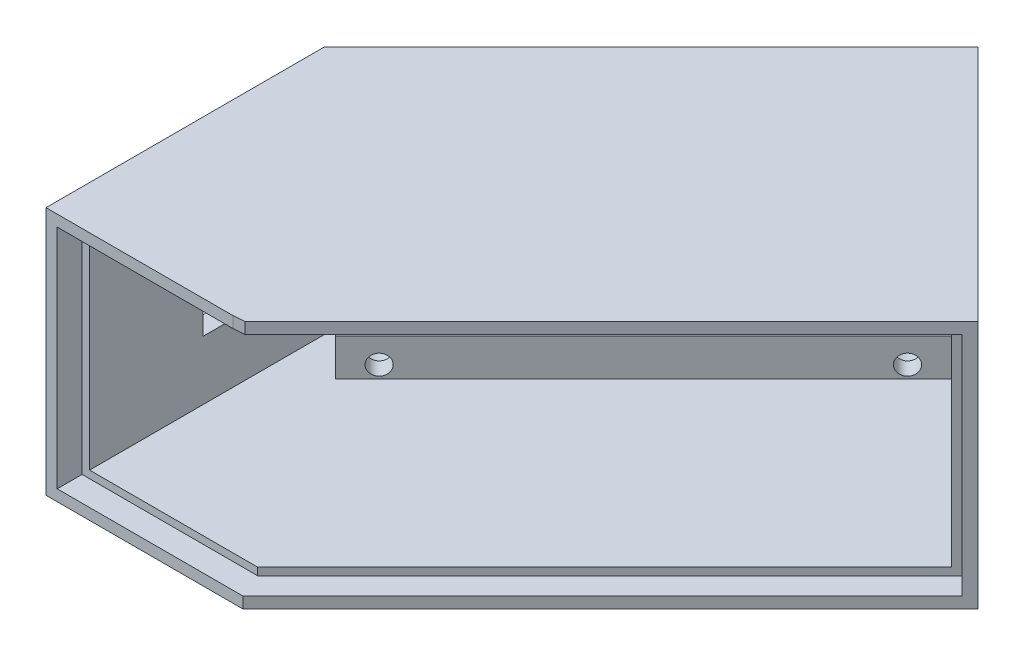
SolidWorks part; units mm, degrees
ref_plane "Спереди" through (0, 0, 0) normal (0, 0, 1) x (1, 0, 0)
ref_plane "Сверху" through (0, 0, 0) normal (0, 1, 0) x (1, 0, 0)
ref_plane "Справа" through (0, 0, 0) normal (1, 0, 0) x (0, 0, -1)
sketch "Sketch1" plane through (0, 0, 0) normal (0, 1, 0) x (1, 0, 0)
  line L0 (-43.3594, -5.3943) -> (-43.3594, 35.3164)
  line L1 (-43.3594, 35.3164) -> (9.115, 87.7907)
  line L2 (9.115, 87.7907) -> (44.4704, 52.4354)
  line L3 (44.4704, 52.4354) -> (-13.3594, -5.3943)
  line L4 (-13.3594, -5.3943) -> (-43.3594, -5.3943)
  dimension "D1" = 74.21
  dimension "D3" = 135
  dimension "D4" = 30
  dimension "D5" = 50
extrude "Boss-Extrude1" add sketch "Sketch1" along normal blind 40
shell "Shell1" thickness 3 removed face at (-28.3594, 20, 5.3943) removed face at (15.5555, 20, -23.5205)
sketch "Sketch6" plane through (-3.9825, 0, -3.9825) normal (0.7071, 0, 0.7071) x (0.7071, 0, -0.7071)
  line L0 (-13.2609, 38.2) -> (66.7227, 38.2)
  line L1 (-13.2609, 40) -> (-13.2609, 37) construction
  line L2 (66.7227, 38.2) -> (66.7227, 1.8)
  line L3 (66.7227, 1.8) -> (-13.2609, 1.8)
  line L4 (-13.2609, 3) -> (-13.2609, 0) construction
  line L5 (-13.2609, 40) -> (68.5227, 40) construction
  line L6 (-13.2609, 0) -> (68.5227, 0) construction
  line L7 (68.5227, 40) -> (68.5227, 0) construction
  line L8 (-13.2609, 38.2) -> (-13.2609, 40)
  line L9 (-13.2609, 40) -> (68.5227, 40)
  line L10 (68.5227, 40) -> (68.5227, 0)
  line L11 (68.5227, 0) -> (-13.2609, 0)
  line L12 (-13.2609, 0) -> (-13.2609, 1.8)
  dimension "D1" = 1.8
  dimension "D2" = 1.8
  dimension "D3" = 1.8
extrude "Boss-Extrude2" add sketch "Sketch6" along normal blind 4
sketch "Sketch7" plane through (0, 0, 5.3943) normal (0, 0, 1) x (1, 0, 0)
  line L0 (-13.3594, 1.8) -> (-41.5594, 1.8)
  line L1 (-41.5594, 1.8) -> (-41.5594, 38.2)
  line L2 (-41.5594, 38.2) -> (-13.3594, 38.2)
  line L3 (-43.3594, 40) -> (-43.3594, 0) construction
  line L4 (-13.3594, 38.2) -> (-13.3594, 40)
  line L5 (-13.3594, 40) -> (-43.3594, 40)
  line L6 (-43.3594, 40) -> (-43.3594, 0)
  line L7 (-43.3594, 0) -> (-13.3594, 0)
  line L8 (-13.3594, 0) -> (-13.3594, 1.8)
  dimension "D1" = 1.8
extrude "Boss-Extrude3" add sketch "Sketch7" along normal blind 4
sketch "Sketch8" plane through (0, 0, 0) normal (0, -1, 0) x (1, 0, 0)
  line L0 (-13.3594, 9.3943) -> (-11.7025, 9.3943)
  line L1 (-11.7025, 9.3943) -> (-10.5309, 8.2228)
  line L2 (-10.5309, 8.2228) -> (-13.3594, 5.3943)
  line L3 (-13.3594, 5.3943) -> (-13.3594, 9.3943)
  line L4 (-10.5309, 8.2228) -> (47.2988, -49.607) construction
extrude "Boss-Extrude4" add sketch "Sketch8" against normal up to surface (1.8 mm away) up to face at (16.3333, 1.8, -21.4699)
sketch "Sketch9" plane through (0, 40, 0) normal (0, 1, 0) x (1, 0, 0)
  line L0 (-13.3594, -5.3943) -> (-10.5309, -8.2228)
  line L1 (-10.5309, -8.2228) -> (-11.5537, -9.2455)
  line L2 (-11.5537, -9.2455) -> (-13.3594, -9.3943)
  line L3 (-13.3594, -9.3943) -> (-13.3594, -5.3943)
  line L4 (47.2988, 49.607) -> (-10.5309, -8.2228) construction
extrude "Boss-Extrude5" add sketch "Sketch9" against normal up to surface (1.8 mm away) up to face at (16.3333, 38.2, -21.4699)
sketch "Sketch10" plane through (-37.2165, 0, -37.2165) normal (0.7071, 0, 0.7071) x (0.7071, 0, -0.7071)
  line L0 (65.5227, 20) -> (-4.4446, 20) construction
  line L1 (65.5227, 37) -> (65.5227, 3) construction
  line L2 (-4.4446, 37) -> (-4.4446, 3) construction
  line L3 (60.5227, 35) -> (60.5227, 5) construction
  line L4 (68.5227, 40) -> (68.5227, 0) construction
  line L5 (0.5227, 35) -> (0.5227, 5) construction
  line L6 (60.5227, 35) -> (0.5227, 35) construction
  circle A0 centre (60.5227, 35) radius 1.6
  circle A1 centre (60.5227, 5) radius 1.6
  circle A2 centre (0.5227, 35) radius 1.6
  circle A3 centre (0.5227, 5) radius 1.6
  point P8 (60.5227, 20)
  point P11 (68.5227, 20)
  dimension "D3" = 3.2
  dimension "D1" = 30
  dimension "D2" = 8
  dimension "D4" = 60
extrude "Cut-Extrude6" cut sketch "Sketch10" against normal through all
sketch "Sketch11" plane through (-40.3594, 0, 0) normal (1, 0, 0) x (0, 0, -1)
  line L0 (19.2076, 37) -> (19.2076, 3) construction
  line L1 (34.0737, 37) -> (-5.3943, 37) construction
  line L2 (34.0737, 3) -> (-5.3943, 3) construction
  line L4 (12.8076, 12.5) -> (25.6076, 12.5)
  line L5 (12.8076, 12.5) -> (12.8076, 27.5)
  line L6 (12.8076, 27.5) -> (25.6076, 27.5)
  line L7 (25.6076, 12.5) -> (25.6076, 27.5)
  line L8 (12.8076, 12.5) -> (25.6076, 27.5) construction
  line L9 (12.8076, 27.5) -> (25.6076, 12.5) construction
  point P6 (19.2076, 20)
  dimension "D1" = 15
  dimension "D2" = 12.8
extrude "Cut-Extrude7" cut sketch "Sketch11" against normal up to surface (3 mm away) up to face at (-43.3594, 20, -12.961)
sketch "Sketch12" plane through (-37.2165, 0, -37.2165) normal (0.7071, 0, 0.7071) x (0.7071, 0, -0.7071)
  line L0 (65.5227, 37) -> (-4.4446, 3) construction
  line L1 (-4.4446, 37) -> (-4.4446, 3) construction
  line L3 (65.5227, 3) -> (-4.4446, 3)
  line L4 (65.5227, 3) -> (65.5227, 37)
  line L5 (65.5227, 37) -> (-4.4446, 37)
  line L6 (-4.4446, 3) -> (-4.4446, 37)
  line L7 (65.5227, 3) -> (-4.4446, 37) construction
  line L8 (65.5227, 37) -> (-4.4446, 3) construction
  circle A0 centre (0.5227, 35) radius 1.6
  circle A1 centre (60.5227, 35) radius 1.6
  circle A2 centre (60.5227, 5) radius 1.6
  circle A3 centre (0.5227, 5) radius 1.6
  point P5 (30.539, 20)
extrude "Boss-Extrude7" add sketch "Sketch12" along normal blind 10
sketch "Sketch13" plane through (-39.3379, 0, -39.3379) normal (-0.7071, 0, -0.7071) x (-0.7071, 0, 0.7071)
  circle A0 centre (-0.5227, 35) radius 3.1
  circle A1 centre (-0.5227, 5) radius 3.1
  circle A2 centre (-60.5227, 5) radius 3.1
  circle A3 centre (-60.5227, 35) radius 3.1
  dimension "D1" = 6.2
extrude "Cut-Extrude9" cut sketch "Sketch13" against normal blind 10
sketch "Sketch14" plane through (-30.1455, 0, -30.1455) normal (0.7071, 0, 0.7071) x (0.7071, 0, -0.7071)
  line L0 (-4.4446, 37) -> (65.5227, 3) construction
  line L1 (-4.4446, 37) -> (-4.4446, 3) construction
  line L2 (65.5227, 9) -> (-4.4446, 9)
  line L3 (65.5227, 9) -> (65.5227, 31)
  line L4 (65.5227, 31) -> (-4.4446, 31)
  line L5 (-4.4446, 9) -> (-4.4446, 31)
  line L6 (65.5227, 9) -> (-4.4446, 31) construction
  line L7 (65.5227, 31) -> (-4.4446, 9) construction
  point P4 (30.539, 20)
  dimension "D1" = 22
extrude "Cut-Extrude10" cut sketch "Sketch14" against normal blind 10
